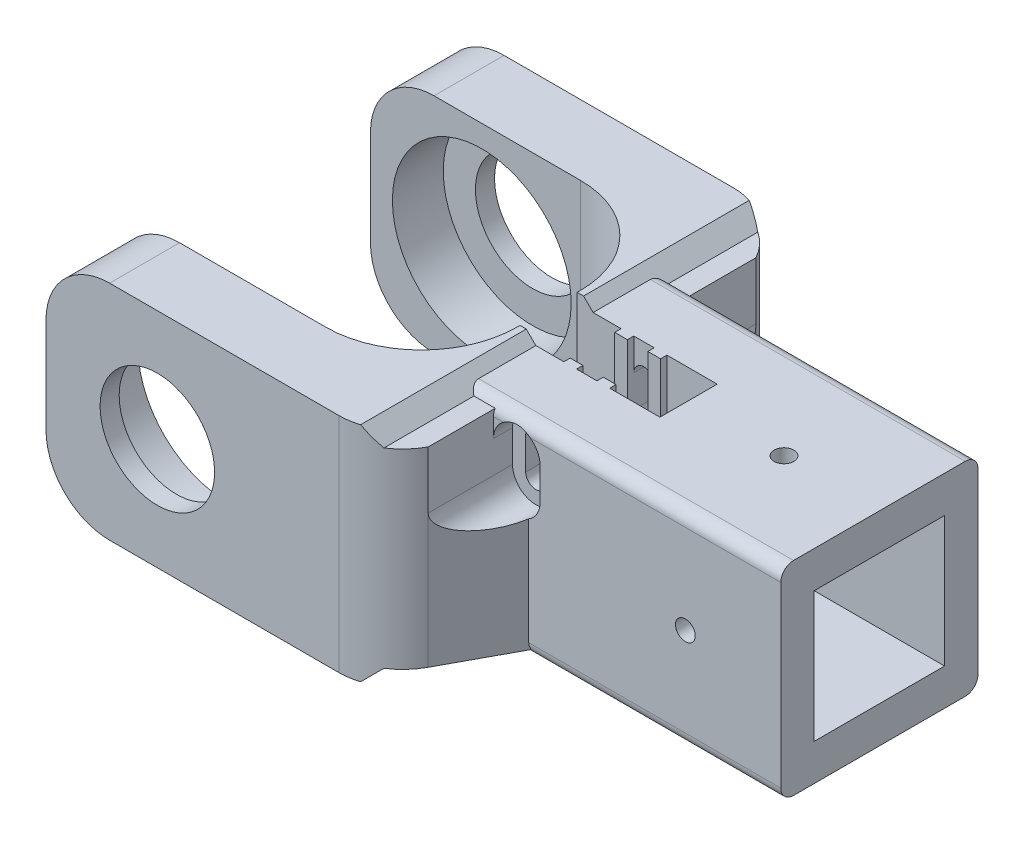
SolidWorks part; units mm, degrees
ref_plane "Piano frontale" through (0, 0, 0) normal (0, 0, 1) x (1, 0, 0)
ref_plane "Piano superiore" through (0, 0, 0) normal (0, 1, 0) x (1, 0, 0)
ref_plane "Piano destro" through (0, 0, 0) normal (1, 0, 0) x (0, 0, -1)
sketch "Schizzo11" plane through (0, 0, 0) normal (0, 0, 1) x (1, 0, 0)
  line L0 (-14.5, 15) -> (14.5, -15) construction
  line L1 (-14.5, 15) -> (14.5, 15)
  line L3 (-14.5, -15) -> (14.5, -15)
  line L4 (14.5, 15) -> (14.5, -15)
  line L5 (-14.5, -15) -> (-20.5, -15)
  line L6 (-20.5, -15) -> (-20.5, 15)
  line L7 (-20.5, 15) -> (-14.5, 15)
  line L8 (0, 15) -> (0, 0)
  line L9 (0, 0) -> (14.5, 0)
  point P5 (0, -15)
  dimension "D1" = 30
  dimension "D2" = 29
  dimension "D3" = 35
extrude "Estrusione-Estrusione4" add sketch "Schizzo11" along normal blind 29 contours L0 L7 L6 L5 L3 | L1 L0 L8 | L8 L9 L4 L1 | L9 L0 L4 region at (-4.8333, 10, 0) region at (-8.5407, -3.5366, 0) region at (9.6667, -5, 0) region at (7.25, 7.5, 0)
sketch "Schizzo12" plane through (14.5, 0, 0) normal (1, 0, 0) x (0, 0, -1)
  line L1 (-4.25, -10.25) -> (-24.75, -10.25)
  line L2 (-4.25, -10.25) -> (-4.25, 10.25)
  line L3 (-4.25, 10.25) -> (-24.75, 10.25)
  line L4 (-24.75, -10.25) -> (-24.75, 10.25)
  line L5 (-4.25, -10.25) -> (-24.75, 10.25) construction
  line L6 (-4.25, 10.25) -> (-24.75, -10.25) construction
  line L8 (-29, 15) -> (0, -15) construction
  point P0 (-14.5, 0)
  point P8 (-14.5, 0)
  dimension "D2" = 20.5
  dimension "D3" = 20.5
extrude "Taglio-Estrusione5" cut sketch "Schizzo12" against normal blind 31
sketch "Schizzo13" plane through (0, -15, 0) normal (0, -1, 0) x (1, 0, 0)
  line L2 (14.5, 29) -> (14.5, 0) construction
  circle A0 centre (0, 14.5) radius 1.5
  point P9 (14.5, 14.5)
  dimension "D2" = 3
extrude "Taglio-Estrusione6" cut sketch "Schizzo13" against normal through all
sketch "Schizzo14" plane through (0, 0, 29) normal (0, 0, 1) x (1, 0, 0)
  line L1 (14.5, 15) -> (14.5, -15) construction
  circle A0 centre (0, 0) radius 1.5
  point P9 (14.5, 0)
  dimension "D1" = 3
extrude "Taglio-Estrusione7" cut sketch "Schizzo14" against normal through all both and the other way through all
fillet "Raccordo6" radius 2 4 edges at (-3, -15, 0) (-3, -15, 29) (-3, 15, 0) (-3, 15, 29)
sketch "Schizzo15" plane through (-20.5, 0, 0) normal (-1, 0, 0) x (0, 0, 1)
  line L0 (27, 15) -> (2, 15) construction
  line L1 (45.5, -17.5) -> (-16.5, -17.5)
  line L2 (45.5, -17.5) -> (45.5, 17.5)
  line L3 (45.5, 17.5) -> (-16.5, 17.5)
  line L4 (-16.5, -17.5) -> (-16.5, 17.5)
  line L5 (45.5, -17.5) -> (-16.5, 17.5) construction
  line L6 (45.5, 17.5) -> (-16.5, -17.5) construction
  line L7 (29, -13) -> (29, 13) construction
  point P0 (14.5, 0)
  point P8 (14.5, 15)
  point P13 (29, 0)
  dimension "D1" = 35
  dimension "D2" = 62
extrude "Estrusione-Estrusione5" add sketch "Schizzo15" against normal offset from surface (2 mm away) 2 contours L2 L1 L4 L3 up to face at (-16.5, 0, 14.5)
sketch "Schizzo16" plane through (-20.5, 0, 0) normal (-1, 0, 0) x (0, 0, 1)
  line L0 (45.5, -17.5) -> (-16.5, -17.5) construction
  line L1 (-16.5, 17.5) -> (-5.5, 17.5)
  line L2 (-16.5, 17.5) -> (-16.5, -17.5)
  line L3 (-16.5, -17.5) -> (-5.5, -17.5)
  line L4 (-5.5, 17.5) -> (-5.5, -17.5)
  line L5 (45.5, 17.5) -> (-16.5, 17.5) construction
  line L6 (45.5, -17.5) -> (34.5, -17.5)
  line L7 (45.5, -17.5) -> (45.5, 17.5)
  line L8 (45.5, 17.5) -> (34.5, 17.5)
  line L9 (34.5, -17.5) -> (34.5, 17.5)
  line L11 (-16.5, -17.5) -> (-16.5, 17.5) construction
  dimension "D1" = 11
  dimension "D2" = 11
  dimension "D3" = 40
  dimension "D4" = 35
  dimension "D5" = 35
extrude "Estrusione-Estrusione6" add sketch "Schizzo16" along normal blind 50
sketch "Schizzo19" plane through (0, 0, 34.5) normal (0, 0, -1) x (-1, 0, 0)
  line L0 (70.5, 17.5) -> (70.5, -17.5) construction
  circle A0 centre (53, 0) radius 14.05
  dimension "D2" = 28.1
  dimension "D1" = 17.5
sketch "Schizzo20" plane through (0, 0, 34.5) normal (0, 0, -1) x (-1, 0, 0)
  line L0 (70.5, 17.5) -> (70.5, -17.5) construction
  circle A0 centre (53, 0) radius 9
  dimension "D2" = 18
  dimension "D1" = 17.5
extrude "Taglio-Estrusione8" cut sketch "Schizzo19" against normal blind 8
extrude "Taglio-Estrusione9" cut sketch "Schizzo20" against normal through all both and the other way through all
ref_plane "Piano1" through (0, 0, 14.5) normal (0, 0, -1) x (-1, 0, 0)
mirror "Specchia1" about plane through (0, 0, 14.5) normal (0, 0, -1) of "Taglio-Estrusione8"
sketch "Schizzo21" plane through (0, -17.5, 0) normal (0, -1, 0) x (1, 0, 0)
  line L0 (-70.5, 34.5) -> (-20.5, 34.5) construction
  line L1 (-20.5, 34.5) -> (-20.5, -5.5) construction
  line L2 (-70.5, -5.5) -> (-20.5, -5.5) construction
  line L3 (-22.5, -5.5) -> (-22.5, 34.5)
  line L4 (-18.5, 45.5) -> (-8.5, 27)
  line L6 (-8.5, 27) -> (-18.5, 27)
  line L7 (-18.5, 27) -> (-18.5, 45.5)
  line L8 (-18.5, -16.5) -> (-18.5, 2)
  line L9 (-18.5, 2) -> (14.5, 2) construction
  line L10 (-18.5, 0) -> (-18.5, 2) construction
  line L11 (-18.5, 2) -> (-8.5, 2)
  line L12 (-8.5, 2) -> (-18.5, -16.5)
  circle A0 centre (-37.5, 9.5) radius 15
  circle A1 centre (-37.5, 19.5) radius 15
  line M7 (-70.5, 34.5) -> (-20.5, 34.5)
  line M8 (-20.5, 34.5) -> (-20.5, -5.5)
  line M9 (-20.5, -5.5) -> (-70.5, -5.5)
  dimension "D3" = 10
  dimension "D1" = 10
  dimension "D2" = 2
extrude "Estrusione-Estrusione7" add sketch "Schizzo21" against normal up to surface (35 mm away) contours A1 L3 M7 | A0 L3 M9 | L3 M9 M8 M7 region at (-25.8505, -17.5, -2.1495) region at (-21.5, -17.5, 14.5) region at (-25.8505, -17.5, 31.1495) up to face at (-45, 17.5, 14.5)
sketch "Schizzo22" plane through (0, -15, 0) normal (0, -1, 0) x (1, 0, 0)
  line L0 (-18.5, 27) -> (-8.5, 27)
  line L1 (14.5, 27) -> (-18.5, 27) construction
  line L2 (-8.5, 27) -> (-18.5, 45.5)
  line L3 (-18.5, 45.5) -> (-18.5, 27)
  line L4 (-18.5, 2) -> (-18.5, -16.5)
  line L5 (-18.5, -16.5) -> (-8.5, 2)
  line L6 (-18.5, 2) -> (14.5, 2) construction
  line L7 (-8.5, 2) -> (-18.5, 2)
  dimension "D1" = 10
  dimension "D2" = 10
extrude "Estrusione-Estrusione8" add sketch "Schizzo22" against normal up to surface (30 mm away) up to face at (-2, 15, 14.5)
chamfer "Smusso1" distance 3 angle 45 2 edges at (-18.5, -17.5, 14.5) (-18.5, 17.5, 14.5)
fillet "Raccordo8" radius 10 2 edges at (-18.5, 0, 45.5) (-18.5, 0, -16.5)
fillet "Raccordo9" radius 10 4 edges at (-70.5, 17.5, 40) (-70.5, 17.5, -11) (-70.5, -17.5, -11) (-70.5, -17.5, 40)
sketch "Schizzo24" plane through (14.5, 0, 0) normal (1, 0, 0) x (0, 0, -1)
  line L0 (0, 13) -> (0, -13) construction
  line L1 (-24.75, -10.25) -> (-4.25, -10.25)
  line L2 (-24.75, -10.25) -> (-24.75, 10.25)
  line L3 (-24.75, 10.25) -> (-4.25, 10.25)
  line L4 (-4.25, -10.25) -> (-4.25, 10.25)
  line L5 (-30, -16) -> (1, -16)
  line L6 (-30, -16) -> (-30, 16)
  line L7 (-30, 16) -> (1, 16)
  line L8 (1, -16) -> (1, 16)
  line L9 (-29, -13) -> (-29, 13) construction
  line L10 (-27, 15) -> (-2, 15) construction
  line L11 (-43.8765, -15) -> (14.8765, -15) construction
  dimension "D1" = 1
  dimension "D2" = 1
  dimension "D3" = 1
  dimension "D4" = 1
extrude "Estrusione-Estrusione9" add sketch "Schizzo24" along normal blind 15 and the other way up to surface (37 mm away) other way up to face at (-22.5, 0, 14.5)
sketch "Schizzo25" plane through (0, 16, 0) normal (0, 1, 0) x (1, 0, 0)
  line L0 (29.5, 1) -> (29.5, -30) construction
  circle A0 centre (14.5, -14.5) radius 1.55
  point P4 (29.5, -14.5)
  dimension "D1" = 3.1
  dimension "D2" = 15
extrude "Taglio-Estrusione11" cut sketch "Schizzo25" against normal through all both and the other way through all
sketch "Schizzo26" plane through (0, 0, -1) normal (0, 0, -1) x (-1, 0, 0)
  line L0 (-29.5, -16) -> (-29.5, 16) construction
  circle A0 centre (-14.5, 0) radius 1.55
  dimension "D1" = 3.1
  dimension "D2" = 15
extrude "Taglio-Estrusione12" cut sketch "Schizzo26" against normal through all both and the other way through all
sketch "Schizzo28" plane through (0, 0, -1) normal (0, 0, -1) x (-1, 0, 0)
  line L0 (0.5, 6) -> (0.5, -16)
  line L1 (20, -16) -> (-29.5, -16) construction
  line L2 (0.5, -16) -> (20, -16)
  line L3 (20, -16) -> (20, -2.2614)
  circle A0 centre (12, 6) radius 11.5
  line M10 (-29.5, -16) -> (20, -16)
  line M11 (20, -16) -> (19, -15)
  line M12 (19, -15) -> (10.1216, -15)
  line M13 (10.1216, -15) -> (10.1216, 15)
  dimension "D1" = 23
  dimension "D2" = 12
  dimension "D3" = 6
extrude "Estrusione-Estrusione10" add sketch "Schizzo28" against normal up to surface (25.75 mm away) contours A0 L0 M10 M11 M12 M13 | A0 L3 M13 M12 M11 region at (-5.491, -9.4755, -1) region at (-15.3156, -9.8215, -1) up to face at (16.05, 0, 24.75)
sketch "Schizzo32" plane through (0, 0, 30) normal (0, 0, 1) x (1, 0, 0)
  line L0 (-0.5, 16) -> (-0.5, -16)
  line L1 (-20, 16) -> (29.5, 16) construction
  line L2 (-20, -16) -> (29.5, -16) construction
  line L3 (-0.5, -16) -> (-22.5, -16)
  line L4 (29.5, 16) -> (29.5, -16) construction
  line L5 (-22.5, -16) -> (-22.5, 16)
  line L6 (-22.5, 16) -> (-0.5, 16)
  point P6 (0, 0)
  dimension "D1" = 30
  dimension "D2" = 52
extrude "Estrusione-Estrusione11" add sketch "Schizzo32" against normal up to surface (31 mm away) up to face at (-4.9054, 0, -1)
sketch "Schizzo23" plane through (0, 0, 14.5) normal (0, 0, -1) x (-1, 0, 0)
  line L0 (0.5, 6) -> (0.5, 17.5)
  line L2 (23.5, 6) -> (24.462, 17.5)
  line L3 (24.462, 17.5) -> (0.5, 17.5)
  circle A0 centre (12, 6) radius 11.5
  circle A1 centre (53, 0) radius 28 construction
  point P7 (0, 0)
  point P8 (0, 0)
  point P13 (12, 6)
  point P15 (0, 0)
  dimension "D1" = 23
  dimension "D2" = 56
  dimension "D3" = 6
  dimension "D4" = 12
extrude "Taglio-Estrusione10" cut sketch "Schizzo23" against normal blind 4.5 and the other way blind 4.5 contours A0 L3 L0 | A0 L2 L3 | A0 L3 region at (-12, 6, 14.5) region at (-3.0687, 14.9313, 14.5) region at (-21.4026, 14.725, 14.5)
sketch "Schizzo29" plane through (0, 0, -1) normal (0, 0, -1) x (-1, 0, 0)
  line L0 (10.4, 6) -> (10.4, 11)
  line L1 (13.6, 11) -> (13.6, 6)
  circle A0 centre (12, 6) radius 11.5
  circle A1 centre (12, 6) radius 1.6
  circle A2 centre (12, 11) radius 1.6
  point P10 (13.6, 6)
  point P11 (0, 0)
  point P12 (10.4, 11)
  dimension "D1" = 23
  dimension "D3" = 12
  dimension "D4" = 3.2
  dimension "D5" = 3.2
  dimension "D2" = 6
  dimension "D6" = 5
extrude "Taglio-Estrusione13" cut sketch "Schizzo29" against normal through all both and the other way through all contours A1 | A2 L0 A1 L1 | A2 region at (-12, 8.5, -1) region at (-12, 6, -1) region at (-12, 11, -1)
sketch "Schizzo30" plane through (0, 0, -1) normal (0, 0, -1) x (-1, 0, 0)
  line L0 (12, 11) -> (12, 6) construction
  line L1 (13.6, 11) -> (13.6, 6)
  line L2 (10.4, 11) -> (10.4, 6)
  line L3 (13.6, 11) -> (13.6, 6) construction
  line L4 (12, 6) -> (12, 11) construction
  line L5 (8.335, 6) -> (8.335, 11)
  line L6 (15.665, 6) -> (15.665, 11)
  line L7 (15.665, -15) -> (15.665, 15) construction
  arc A0 (13.6, 11) -> (10.4, 11) centre (12, 11) ccw
  arc A1 (10.4, 6) -> (13.6, 6) centre (12, 6) ccw
  arc A2 (8.335, 6) -> (15.665, 6) centre (12, 6) ccw
  arc A3 (15.665, 11) -> (8.335, 11) centre (12, 11) ccw
  point P4 (12, 8.5)
  point P13 (12, 8.5)
extrude "Taglio-Estrusione14" cut sketch "Schizzo30" along normal through all and the other way blind 2
sketch "Schizzo31" plane through (0, 0, 30) normal (0, 0, 1) x (1, 0, 0)
  line L0 (-12, 6) -> (-12, 11) construction
  line L1 (-13.6, 6) -> (-13.6, 11)
  line L2 (-10.4, 6) -> (-10.4, 11)
  line L3 (-10.4, 11) -> (-10.4, 6) construction
  line L4 (-12, 11) -> (-12, 6) construction
  line L5 (-8.335, 11) -> (-8.335, 6)
  line L6 (-15.665, 11) -> (-15.665, 6)
  line L7 (-15.665, 15) -> (-15.665, -15) construction
  arc A0 (-13.6, 6) -> (-10.4, 6) centre (-12, 6) ccw
  arc A1 (-10.4, 11) -> (-13.6, 11) centre (-12, 11) ccw
  arc A2 (-8.335, 11) -> (-15.665, 11) centre (-12, 11) ccw
  arc A3 (-15.665, 6) -> (-8.335, 6) centre (-12, 6) ccw
  point P4 (-12, 8.5)
  point P13 (-12, 8.5)
extrude "Taglio-Estrusione15" cut sketch "Schizzo31" against normal blind 3 and the other way through all
sketch "Schizzo33" plane through (0, 0, 30) normal (0, 0, 1) x (1, 0, 0)
  line L0 (-15.665, 11) -> (-15.665, 6) construction
  line L1 (-15.665, 8.5) -> (-8.335, 8.5)
  line L2 (-15.665, 8.5) -> (-15.665, 15)
  line L3 (-15.665, 15) -> (-8.335, 15)
  line L4 (-8.335, 8.5) -> (-8.335, 15)
  line L5 (-19, 15) -> (-10.1216, 15) construction
  line L6 (-8.335, 11) -> (-8.335, 6) construction
extrude "Taglio-Estrusione16" cut sketch "Schizzo33" along normal through all
mirror "Specchia2" about plane through (0, 0, 14.5) normal (0, 0, -1) of "Taglio-Estrusione16"
sketch "Schizzo34" plane through (0, 0, 10) normal (0, 0, 1) x (1, 0, 0)
  line L0 (-20, 16) -> (29.5, 16) construction
  line L3 (-10.4, 16) -> (-8.4, 16)
  line L6 (-13.6, 11) -> (-13.6, 6) construction
  line L7 (-10.4, 16) -> (-10.4, 2.335)
  line L8 (-10.4, 2.335) -> (-8.4, 2.335)
  line L9 (-8.4, 16) -> (-8.4, 2.335)
  line L10 (-13.6, 16) -> (-15.6, 16)
  line L11 (-13.6, 16) -> (-13.6, 2.335)
  line L12 (-13.6, 2.335) -> (-15.6, 2.335)
  line L13 (-15.6, 16) -> (-15.6, 2.335)
  line L14 (-10.4, 6) -> (-10.4, 11) construction
  arc A2 (-15.665, 6) -> (-8.335, 6) centre (-12, 6) ccw construction
  dimension "D1" = 2
  dimension "D2" = 2
extrude "Estrusione-Estrusione12" add sketch "Schizzo34" along normal blind 1
mirror "Specchia3" about plane through (0, 0, 14.5) normal (0, 0, -1) of "Estrusione-Estrusione12"
fillet "Raccordo10" radius 2 4 edges at (4.75, -16, 30) (4.75, -16, -1) (4.75, 16, 30) (4.75, 16, -1)
